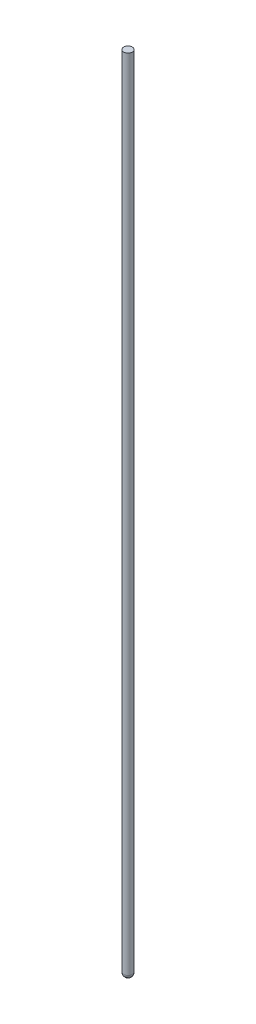
SolidWorks part; units mm, degrees
ref_plane "Front Plane" through (0, 0, 0) normal (0, 0, 1) x (1, 0, 0)
ref_plane "Top Plane" through (0, 0, 0) normal (0, 1, 0) x (1, 0, 0)
ref_plane "Right Plane" through (0, 0, 0) normal (1, 0, 0) x (0, 0, -1)
sketch "Sketch1" plane through (0, 0, 0) normal (0, 1, 0) x (1, 0, 0)
  circle A0 centre (0, 0) radius 5.08
extrude "Boss-Extrude1" add sketch "Sketch1" along normal blind 934.72
fillet "Fillet1" radius 4.953 1 edges at (0, 0, 5.08)
